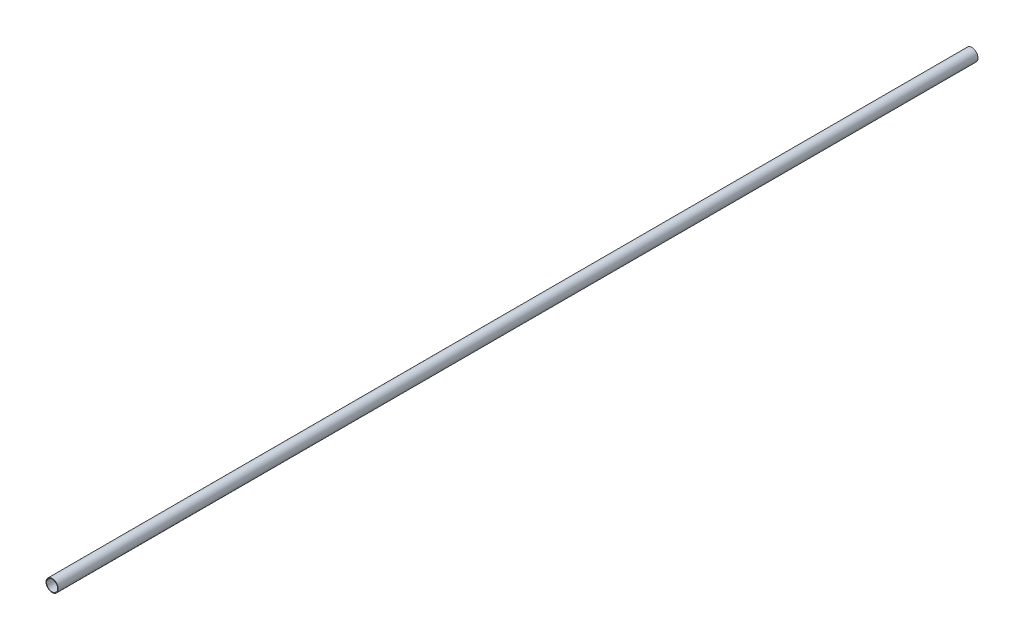
SolidWorks part; units mm, degrees
material "carbon fiber"
ref_plane "Front Plane" through (0, 0, 0) normal (0, 0, 1) x (1, 0, 0)
ref_plane "Top Plane" through (0, 0, 0) normal (0, 1, 0) x (1, 0, 0)
ref_plane "Right Plane" through (0, 0, 0) normal (1, 0, 0) x (0, 0, -1)
sketch "Эскиз1" plane through (0, 0, 0) normal (0, 0, 1) x (1, 0, 0)
  circle A0 centre (0, 0) radius 10
  circle A1 centre (0, 0) radius 9
  dimension "D1" = 20
  dimension "D2" = 1
extrude "Бобышка-Вытянуть1" add sketch "Эскиз1" along normal mid plane 1500
